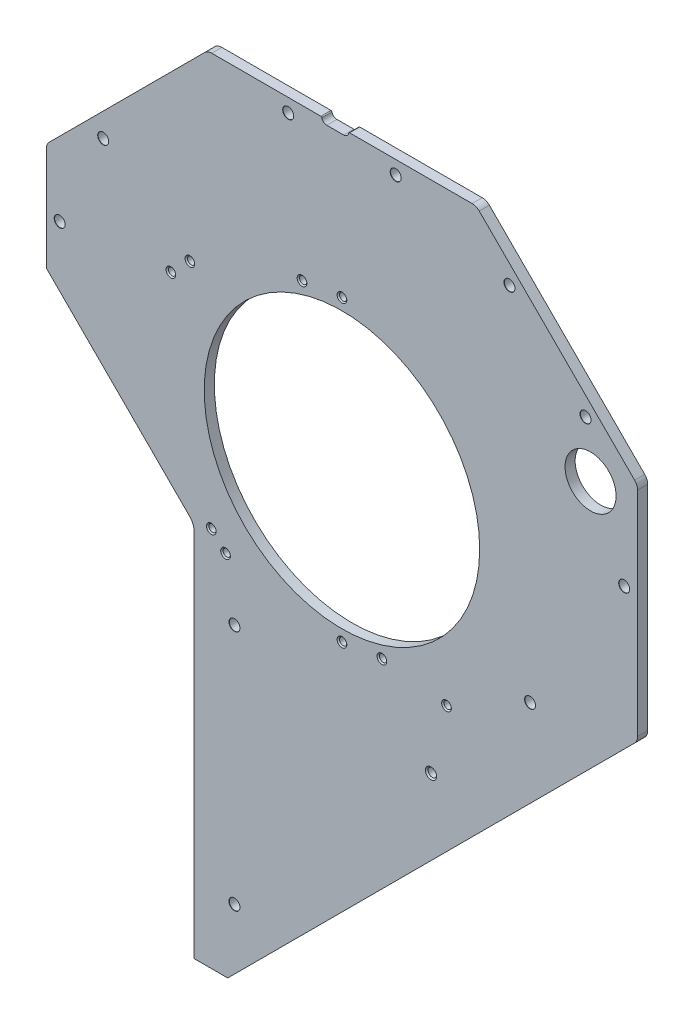
SolidWorks part; units mm, degrees
material "6061-T6 (SS)"
ref_plane "Front Plane" through (0, 0, 0) normal (0, 0, 1) x (1, 0, 0)
ref_plane "Top Plane" through (0, 0, 0) normal (0, 1, 0) x (1, 0, 0)
ref_plane "Right Plane" through (0, 0, 0) normal (1, 0, 0) x (0, 0, -1)
ref_axis "Axis1" through (0, 0, 30.8633) along (0, 0, -1)
sketch "Sketch1" plane through (0, 0, 0) normal (0, 0, 1) x (1, 0, 0)
  line L0 (-63.5, 139.7) -> (-139.7, 63.5)
  line L2 (-139.7, 63.5) -> (-139.7, 12.7)
  line L3 (-69.85, -234.95) -> (-53.975, -234.95)
  line L4 (139.7, 63.5) -> (139.7, -41.275)
  line L5 (63.5, 139.7) -> (139.7, 63.5)
  line L6 (-63.5, 139.7) -> (63.5, 139.7)
  line L7 (-139.7, 12.7) -> (-71.9331, -55.0669)
  line L8 (-69.85, -60.0959) -> (-69.85, -234.95)
  line L10 (-53.975, -234.95) -> (139.7, -41.275)
  arc A0 (-71.9331, -55.0669) -> (-69.85, -60.0959) centre (-76.962, -60.0959) cw
  circle A1 centre (0, 0) radius 65.0875
  dimension "D5" = 130.175
  dimension "D6" = 45
  dimension "D14" = 7.112
  dimension "D1" = 234.95
  dimension "D2" = 45
  dimension "D3" = 139.7
  dimension "D4" = 139.7
  dimension "D7" = 139.7
  dimension "D8" = 76.2
  dimension "D9" = 41.275
  dimension "D10" = 12.7
  dimension "D11" = 45
  dimension "D12" = 69.85
  dimension "D13" = 45
  dimension "D15" = 63.5
extrude "Boss-Extrude1" add sketch "Sketch1" along normal blind 4.7752
sketch "Sketch5" plane through (0, 0, 0) normal (0, 0, 1) x (1, 0, 0)
  circle A2 centre (117.475, 53.975) radius 12.065
  dimension "D5" = 117.475
  dimension "D6" = 53.975
  dimension "D7" = 24.13
extrude "Cut-Extrude2" cut sketch "Sketch5" along normal through all
hole_wizard "#8-32 Tapped Hole1" positions "Sketch7" profile "Sketch6" tap size "#8-32" standard "Ansi Inch" end condition through all
sketch "Sketch7" plane through (-61.2466, -44.3804, 0) normal (0, 0, -1) x (-1, 0, 0)
  line L0 (-39.918, 65.709) -> (-17.767, 87.86) construction
  line L1 (10.5955, 93.7718) -> (19.5758, 84.7916) construction
  line L3 (-110.638, -27.4616) -> (-101.6577, -36.4419) construction
  line L5 (2.2534, 184.0804) -> (-124.7466, 184.0804) construction
  line L6 (0.4837, -10.6326) -> (-6.2335, -17.3498) construction
  point P21 (10.5955, 93.7718)
  point P23 (19.5758, 84.7916)
  point P25 (-110.638, -27.4616)
  point P52 (0.4837, -10.6326)
  point P57 (-6.2335, -17.3498)
  dimension "D1" = 45
  dimension "D2" = 85.725
  dimension "D3" = 85.725
  dimension "D4" = 15.875
  dimension "D5" = 12.7
  dimension "D6" = 15.875
  dimension "D8" = 82.55
  dimension "D9" = 80.9752
  dimension "D10" = 9.4996
  dimension "D11" = 80.9752
sketch "Sketch6" plane through (-71.842, 49.3914, 0) normal (1, 0, 0) x (0, 1, 0)
  line L0 (0, 0) -> (0, 4.7752)
  line L1 (0, 4.7752) -> (2.286, 4.7752)
  line L2 (1.7272, 4.2164) -> (1.7272, 0.5588)
  line L3 (1.7272, 0.5588) -> (2.286, 0)
  line L5 (2.286, 0) -> (0, 0)
  line L6 (-1.7272, 0.5588) -> (-2.286, 0) construction
  line L7 (2.286, 4.7752) -> (1.7272, 4.2164)
  line L8 (-2.286, 4.7752) -> (-1.7272, 4.2164) construction
  line L11 (0, -6.35) -> (0, 107.95) construction
  dimension "Thru Tap Drill Dia." = 3.4544
  dimension "Thru Tap Drill Depth" = 4.7752
  dimension "Near C'Sink Dia." = 4.572
  dimension "Near C'Sink Angle" = 90
  dimension "Far C'Sink Dia." = 4.572
  dimension "Far C'Sink Angle" = 90
cosmetic thread "Hole Thread8"
cosmetic thread "Hole Thread9"
cosmetic thread "Hole Thread10"
cosmetic thread "Hole Thread11"
cosmetic thread "Hole Thread12"
hole_wizard "#8-32 Tapped Hole2" positions "Sketch17" profile "Sketch16" tap size "#8-32" standard "ANSI Inch" end condition through all
sketch "Sketch17" plane through (0, 0, 0) normal (0, 0, -1) x (-1, 0, 0)
  line L0 (3.7302, 27.3549) -> (9.4377, 69.2095) construction
  line L2 (7.5722, 27.2483) -> (16.0833, 57.8757) construction
  line L4 (18.8753, 67.9225) -> (0, 70.4964) construction
  point P0 (18.8753, 67.9225)
  point P2 (0, 70.4964)
  dimension "D1" = 69.85
  dimension "D2" = 19.05
  dimension "D5" = 7.765
sketch "Sketch16" plane through (-18.8753, 67.9225, 0) normal (1, 0, 0) x (0, 1, 0)
  line L0 (0, 0) -> (0, 4.7752)
  line L1 (0, 4.7752) -> (2.286, 4.7752)
  line L2 (1.7272, 4.2164) -> (1.7272, 0.5588)
  line L3 (1.7272, 0.5588) -> (2.286, 0)
  line L5 (2.286, 0) -> (0, 0)
  line L6 (-1.7272, 0.5588) -> (-2.286, 0) construction
  line L7 (2.286, 4.7752) -> (1.7272, 4.2164)
  line L8 (-2.286, 4.7752) -> (-1.7272, 4.2164) construction
  line L11 (0, -6.35) -> (0, 107.95) construction
  dimension "Thru Tap Drill Dia." = 3.4544
  dimension "Thru Tap Drill Depth" = 4.7752
  dimension "Near C'Sink Dia." = 4.572
  dimension "Near C'Sink Angle" = 90
  dimension "Far C'Sink Dia." = 4.572
  dimension "Far C'Sink Angle" = 90
cosmetic thread "Hole Thread15"
cosmetic thread "Hole Thread16"
pattern_circular "CirPattern1" count 2 over 360 about axis through (0, 0, 30.8633) along (0, 0, -1) of "#8-32 Tapped Hole2" reverse direction yes
sketch "Sketch8" plane through (0, 0, 0) normal (0, 0, 1) x (1, 0, 0)
  line L0 (-35.2844, 35.2844) -> (-8.4481, 8.4481) construction
  line L1 (17.0117, 0) -> (44.4626, 0) construction
  line L2 (-76.3322, 40.4112) -> (-67.3519, 49.3914) construction
  line L3 (47.1463, -69.597) -> (38.1661, -78.5772) construction
  line L4 (-31.3054, -205.5272) -> (112.3787, -61.8431) construction
  line L5 (-53.975, -234.95) -> (139.7, -41.275) construction
  line L6 (-31.3054, -205.5272) -> (3.773, -240.6055) construction
  line L7 (63.5, 139.7) -> (139.7, 63.5) construction
  circle A0 centre (47.1463, -69.597) radius 2.1082 construction
  circle A1 centre (38.1661, -78.5772) radius 2.1082 construction
  circle A2 centre (-76.3322, 40.4112) radius 2.1082 construction
  circle A3 centre (-67.3519, 49.3914) radius 2.1082 construction
  circle A4 centre (47.1463, -69.597) radius 6.35 construction
  circle A5 centre (-31.3054, -205.5272) radius 2.159
  circle A6 centre (4.6157, -169.6062) radius 2.159
  circle A7 centre (76.4577, -97.7641) radius 2.159
  circle A8 centre (112.3787, -61.8431) radius 2.159
  dimension "D2" = 4.2164
  dimension "D3" = 12.7
  dimension "D5" = 12.7
  dimension "D9" = 4.318
  dimension "D12" = 50.8
  dimension "D13" = 101.6
  dimension "D14" = 50.8
  dimension "D15" = 4.7752
  dimension "D1" = 45
  dimension "D4" = 82.55
  dimension "D6" = 15.875
  dimension "D7" = 82.55
  dimension "D8" = 12.7
  dimension "D10" = 36.8349
  dimension "D11" = 107.95
extrude "Cut-Extrude3" [suppressed] cut sketch "Sketch8" along normal up to next
hole_wizard "#7 (0.201) Diameter Hole1" positions "Sketch10" profile "Sketch9" hole size "#7" standard "Ansi Inch" end condition through all
sketch "Sketch10" plane through (0, 0, 0) normal (0, 0, -1) x (-1, 0, 0)
  line L6 (-63.5, 139.7) -> (-139.7, 63.5) construction
  line L7 (63.5, 139.7) -> (139.7, 63.5) construction
  line L8 (63.5, 139.7) -> (-63.5, 139.7) construction
  line L9 (-139.7, 63.5) -> (-139.7, -41.275) construction
  line L10 (-86.8648, 107.3549) -> (-107.3549, 86.8648) construction
  line L12 (-97.1099, 97.1099) -> (-101.6, 101.6) construction
  line L13 (139.7, 63.5) -> (139.7, 12.7) construction
  point P0 (-25.4, 133.35)
  point P1 (-115.0704, 79.1494)
  point P6 (133.35, 34.925)
  point P8 (50.8, -88.9)
  point P11 (-133.35, 19.05)
  point P13 (-88.9, -50.8)
  point P15 (50.8, -203.2)
  point P43 (112.8074, 79.1494)
  point P57 (-79.1494, 115.0704)
  point P71 (25.4, 133.35)
  dimension "D1" = 133.35
  dimension "D2" = 6.35
  dimension "D3" = 25.4
  dimension "D4" = 133.35
  dimension "D5" = 50.8
  dimension "D6" = 88.9
  dimension "D7" = 34.925
  dimension "D8" = 203.2
  dimension "D9" = 133.35
  dimension "D10" = 50.8
  dimension "D11" = 88.9
  dimension "D12" = 19.05
  dimension "D13" = 44.45
  dimension "D14" = 25.4
  dimension "D15" = 7.9502
  dimension "D16" = 6.35
  dimension "D17" = 6.35
  dimension "D18" = 25.4
  dimension "D19" = 25.4
  dimension "D20" = 6.35
sketch "Sketch9" plane through (25.4, 133.35, 0) normal (1, 0, 0) x (0, 1, 0)
  line L0 (0, 0) -> (0, 4.7752)
  line L1 (0, 4.7752) -> (2.6035, 4.7752)
  line L2 (2.5527, 4.6526) -> (2.5527, 0.1226)
  line L3 (2.5527, 0.1226) -> (2.6035, 0)
  line L5 (2.6035, 0) -> (0, 0)
  line L6 (-2.5527, 0.1226) -> (-2.6035, 0) construction
  line L7 (2.6035, 4.7752) -> (2.5527, 4.6526)
  line L8 (-2.6035, 4.7752) -> (-2.5527, 4.6526) construction
  line L11 (0, -6.35) -> (0, 107.95) construction
  dimension "Thru Hole Dia." = 5.1054
  dimension "Thru Hole Depth" = 4.7752
  dimension "Near C'Sink Dia." = 5.207
  dimension "Near C'Sink Angle" = 45
  dimension "Far C'Sink Dia." = 5.207
  dimension "Far C'Sink Angle" = 45
hole_wizard "#10-32 Tapped Hole1" positions "Sketch12" profile "Sketch11" tap size "#10-32" standard "Ansi Inch" end condition up to next
sketch "Sketch12" plane through (0, 0, 0) normal (0, 0, -1) x (-1, 0, 0)
  point P0 (-42.0624, -103.1875)
  dimension "D1" = 42.0624
  dimension "D2" = 103.1875
sketch "Sketch11" plane through (42.0624, -103.1875, 0) normal (1, 0, 0) x (0, 1, 0)
  line L0 (0, 0) -> (0, 4.7752)
  line L1 (0, 4.7752) -> (2.6543, 4.7752)
  line L2 (2.0193, 4.1402) -> (2.0193, 0.5207)
  line L3 (2.0193, 0.5207) -> (2.54, 0)
  line L5 (2.54, 0) -> (0, 0)
  line L6 (-2.0193, 0.5207) -> (-2.54, 0) construction
  line L7 (2.6543, 4.7752) -> (2.0193, 4.1402)
  line L8 (-2.6543, 4.7752) -> (-2.0193, 4.1402) construction
  line L11 (0, -6.35) -> (0, 107.95) construction
  dimension "Thread Major Dia." = 4.0386
  dimension "Thru Tap Drill Depth" = 4.7752
  dimension "Near C'Sink Dia." = 5.08
  dimension "Near C'Sink Angle" = 90
  dimension "Far C'Sink Dia." = 5.3086
  dimension "Far C'Sink Angle" = 90
fillet "Fillet1" radius 4.7752 5 edges at (-139.7, 63.5, 2.3876) (-63.5, 139.7, 2.3876) (63.5, 139.7, 2.3876) (139.7, 63.5, 2.3876) (139.7, -41.275, 2.3876)
sketch "Sketch13" plane through (0, 0, 4.7752) normal (0, 0, 1) x (1, 0, 0)
  line L0 (3.6259, 139.7) -> (9.9265, 140.2512)
  line L1 (-7.1483, 137.414) -> (0.7983, 137.414)
  line L2 (9.9265, 140.2512) -> (9.9265, 142.7707)
  line L3 (-16.2765, 140.2512) -> (-16.2765, 142.7707)
  line L4 (-9.9759, 139.7) -> (-16.2765, 140.2512)
  line L5 (-16.2765, 142.7707) -> (9.9265, 142.7707)
  line L6 (-3.175, 144.6243) -> (-3.175, 150.427) construction
  line L7 (-63.5, 139.7) -> (63.5, 139.7) construction
  arc A0 (-9.9759, 139.7) -> (-9.525, 139.3075) centre (-10.0202, 139.1939) cw
  arc A1 (0.7983, 137.414) -> (3.175, 139.3075) centre (0.7983, 139.8524) ccw
  arc A2 (3.6259, 139.7) -> (3.175, 139.3075) centre (3.6702, 139.1939) ccw
  arc A3 (-7.1483, 137.414) -> (-9.525, 139.3075) centre (-7.1483, 139.8524) cw
  dimension "D3" = 5
  dimension "D1" = 0.508
  dimension "D6" = 2.4384
  dimension "D2" = 2.286
  dimension "D4" = 137.414
  dimension "D5" = 12.7
  dimension "D7" = 3.175
extrude "Cut-Extrude4" cut sketch "Sketch13" against normal up to next
